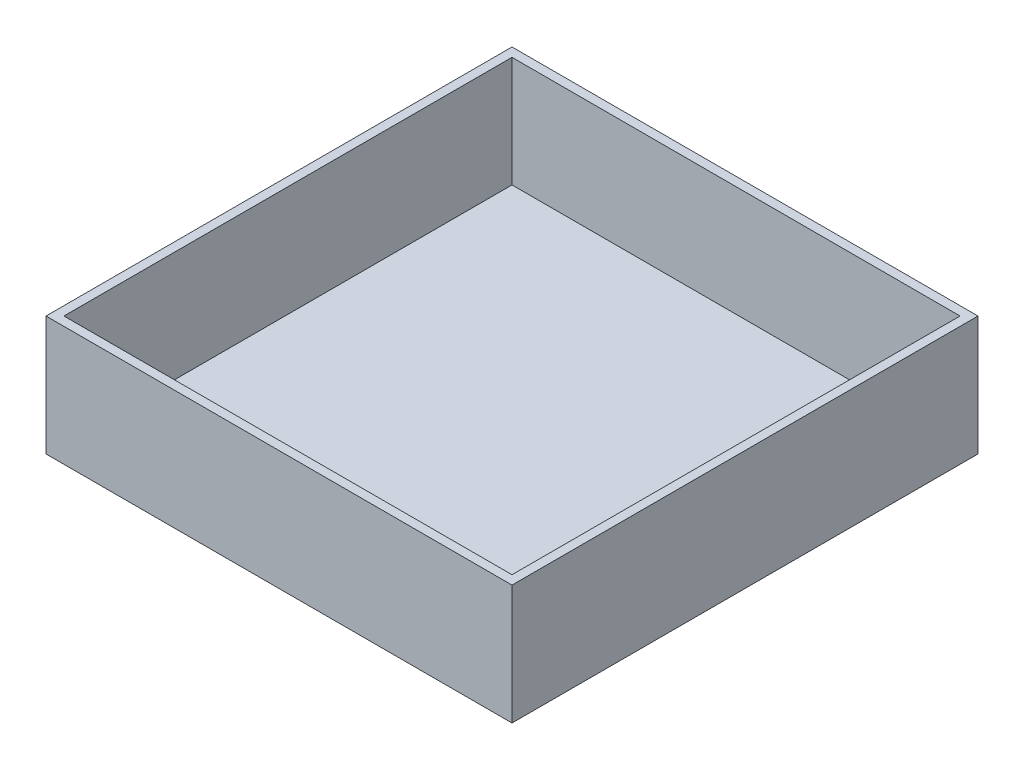
SolidWorks part; units mm, degrees
ref_plane "Front Plane" through (0, 0, 0) normal (0, 0, 1) x (1, 0, 0)
ref_plane "Top Plane" through (0, 0, 0) normal (0, 1, 0) x (1, 0, 0)
ref_plane "Right Plane" through (0, 0, 0) normal (1, 0, 0) x (0, 0, -1)
sketch "Sketch2" plane through (0, 0, 0) normal (0, 1, 0) x (1, 0, 0)
  line L1 (-78, -78) -> (78, -78)
  line L2 (-78, -78) -> (-78, 78)
  line L3 (-78, 78) -> (78, 78)
  line L4 (78, -78) -> (78, 78)
  line L5 (-78, -78) -> (78, 78) construction
  line L6 (-78, 78) -> (78, -78) construction
  line L7 (-75, -75) -> (75, -75)
  line L8 (-75, -75) -> (-75, 75)
  line L9 (-75, 75) -> (75, 75)
  line L10 (75, -75) -> (75, 75)
  line L11 (-75, -75) -> (75, 75) construction
  line L12 (-75, 75) -> (75, -75) construction
  point P0 (0, 0)
  point P6 (0, 0)
  dimension "D1" = 3
  dimension "D2" = 3
  dimension "D3" = 150
  dimension "D4" = 150
extrude "Boss-Extrude1" add sketch "Sketch2" along normal blind 40
extrude "Boss-Extrude2" add sketch "Sketch2<2>" along normal blind 3 contours L7 L10 L9 L8 region at (0, 0, 0)
sketch "Sketch2<2>" plane through (0, 0, 0) normal (0, 1, 0) x (1, 0, 0) same geometry as "Sketch2"
